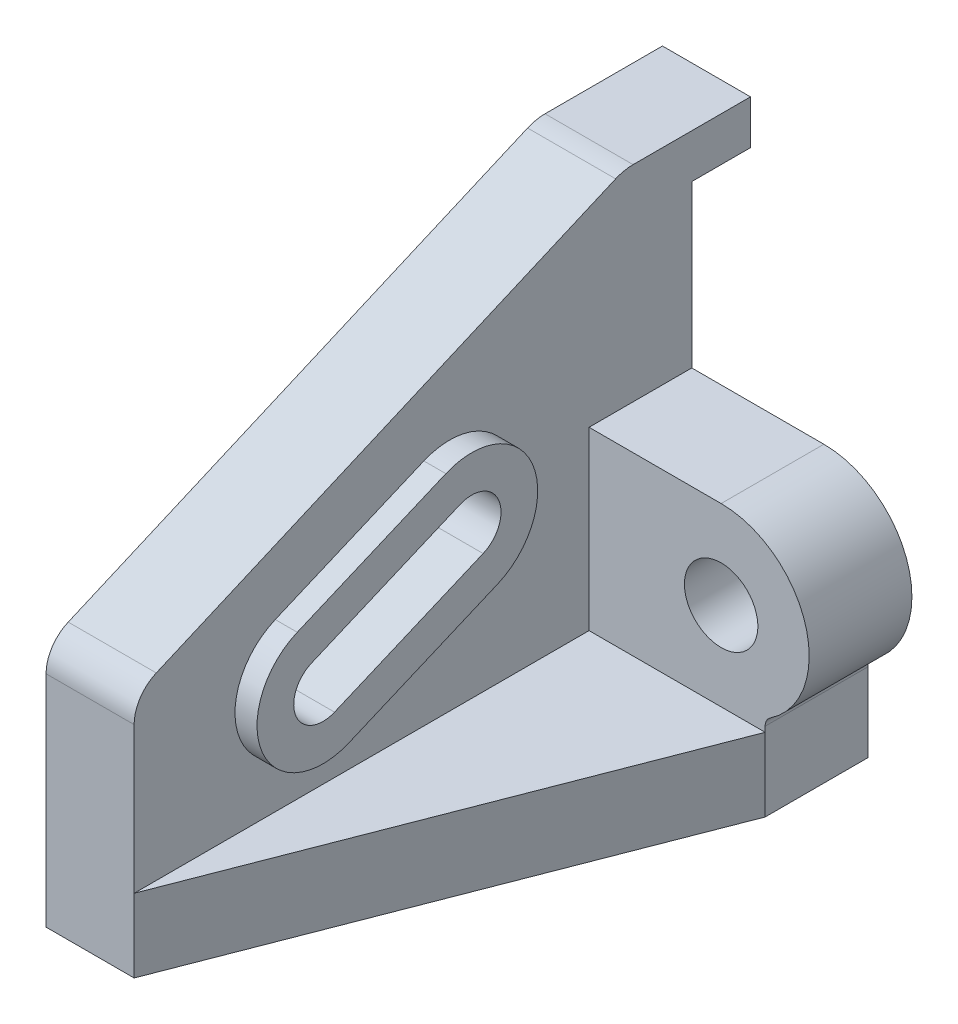
SolidWorks part; units mm, degrees
ref_plane "Front Plane" through (0, 0, 0) normal (0, 0, 1) x (1, 0, 0)
ref_plane "Top Plane" through (0, 0, 0) normal (0, 1, 0) x (1, 0, 0)
ref_plane "Right Plane" through (0, 0, 0) normal (1, 0, 0) x (0, 0, -1)
sketch "Sketch1" plane through (0, 0, 0) normal (1, 0, 0) x (0, 0, -1)
  line L0 (0, 0) -> (98.425, 0)
  line L1 (0, 0) -> (0, 31.6009)
  line L2 (120.65, 0) -> (120.65, 73.025)
  line L3 (120.65, 73.025) -> (133.35, 73.025)
  line L4 (133.35, 73.025) -> (133.35, 82.55)
  line L5 (133.35, 82.55) -> (107.95, 82.55)
  line L6 (104.1765, 81.7706) -> (4.7929, 38.8889)
  line L7 (68.2625, 36.5125) -> (36.1139, 22.8662) construction
  line L8 (33.6327, 28.7114) -> (65.7814, 42.3577)
  line L9 (38.595, 17.021) -> (70.7436, 30.6673)
  line L10 (0, 0) -> (0, -15.875)
  line L11 (0, -15.875) -> (120.65, -15.875)
  line L12 (120.65, -15.875) -> (120.65, 0)
  line L13 (30.5313, 36.0179) -> (62.6799, 49.6642)
  line L14 (41.6964, 9.7145) -> (73.8451, 23.3608)
  line L17 (120.65, 0) -> (120.65, 6.35)
  line L18 (120.65, 6.35) -> (98.425, 6.35)
  line L19 (98.425, 0) -> (98.425, 6.35)
  arc A0 (4.7929, 38.8889) -> (0, 31.6009) centre (7.9375, 31.6009) ccw
  arc A1 (107.95, 82.55) -> (104.1765, 81.7706) centre (107.95, 73.025) ccw
  arc A2 (70.7436, 30.6673) -> (65.7814, 42.3577) centre (68.2625, 36.5125) ccw
  arc A3 (33.6327, 28.7114) -> (38.595, 17.021) centre (36.1139, 22.8662) ccw
  arc A5 (30.5313, 36.0179) -> (41.6964, 9.7145) centre (36.1139, 22.8662) ccw
  arc A6 (73.8451, 23.3608) -> (62.6799, 49.6642) centre (68.2625, 36.5125) ccw
  dimension "D4" = 7.9375
  dimension "D5" = 9.525
  dimension "D7" = 25.4
  dimension "D9" = 12.7
  dimension "D12" = 12.7
  dimension "D15" = 28.575
  dimension "D17" = 28.575
  dimension "D1" = 120.65
  dimension "D2" = 73.025
  dimension "D3" = 12.7
  dimension "D6" = 12.7
  dimension "D8" = 99.3836
  dimension "D10" = 23
  dimension "D11" = 52.3875
  dimension "D13" = 34.925
  dimension "D14" = 15.875
  dimension "D16" = 52.3875
  dimension "D18" = 22.225
  dimension "D19" = 6.35
  dimension "D20" = 6.35
extrude "Boss-Extrude1" add sketch "Sketch1" along normal blind 19.05 contours L11 L12 L0 L10 | L5 A1 L6 A0 L1 L0 L2 L3 L4 A6 L14 A5 L13 | L14 A6 L13 A5 A3 L8 A2 L9 region at (0, 15.8005, -1.5683) region at (0, -7.1749, -63.7023) region at (0, 42.1603, -46.8946)
extrude "Boss-Extrude2" add sketch "Sketch1<3>" along normal blind 4.7625 from surface contours L14 A6 L13 A5 A3 L8 A2 L9 region at (0, 42.1603, -46.8946) starting at face at (19.05, 48.0634, -80.421)
sketch "Sketch1<3>" plane through (0, 0, 0) normal (1, 0, 0) x (0, 0, -1) same geometry as "Sketch1"
extrude "Boss-Extrude3" add sketch "Sketch1<4>" along normal blind 38.1 from surface contours L11 L12 L0 L10 region at (0, -7.1749, -63.7023) starting at face at (19.05, 48.0634, -80.421)
sketch "Sketch1<4>" plane through (0, 0, 0) normal (1, 0, 0) x (0, 0, -1) same geometry as "Sketch1"
sketch "Sketch2" plane through (0, 0, 0) normal (0, 1, 0) x (1, 0, 0)
  line L0 (19.05, 0) -> (57.15, 98.425)
  line L1 (57.15, 98.425) -> (57.15, 0) construction
  line L2 (57.15, 98.425) -> (57.15, 0)
  line L3 (57.15, 0) -> (19.05, 0)
  line L4 (57.15, 120.65) -> (19.05, 120.65) construction
  dimension "D1" = 22.225
extrude "Cut-Extrude1" cut sketch "Sketch2" against normal through all
sketch "Sketch3" plane through (0, 0, -120.65) normal (0, 0, -1) x (-1, 0, 0)
  line L0 (-19.05, 0) -> (-47.625, 0)
  line L1 (-19.05, 6.35) -> (-19.05, 73.025) construction
  line L2 (-47.625, 38.1) -> (-19.05, 38.1)
  line L3 (-19.05, 0) -> (-19.05, 38.1)
  line L4 (-57.15, -15.875) -> (0, -15.875) construction
  arc A0 (-47.625, 38.1) -> (-47.625, 0) centre (-47.625, 19.05) ccw
  circle A1 centre (-47.625, 19.05) radius 7.9375
  dimension "D2" = 38.1
  dimension "D4" = 15.875
  dimension "D1" = 28.575
  dimension "D3" = 19.05
  dimension "D5" = 15.875
extrude "Boss-Extrude5" add sketch "Sketch3" against normal blind 22.225
fillet "Fillet1" radius 2.54 1 edges at (57.15, 2.5522, -109.5375)
